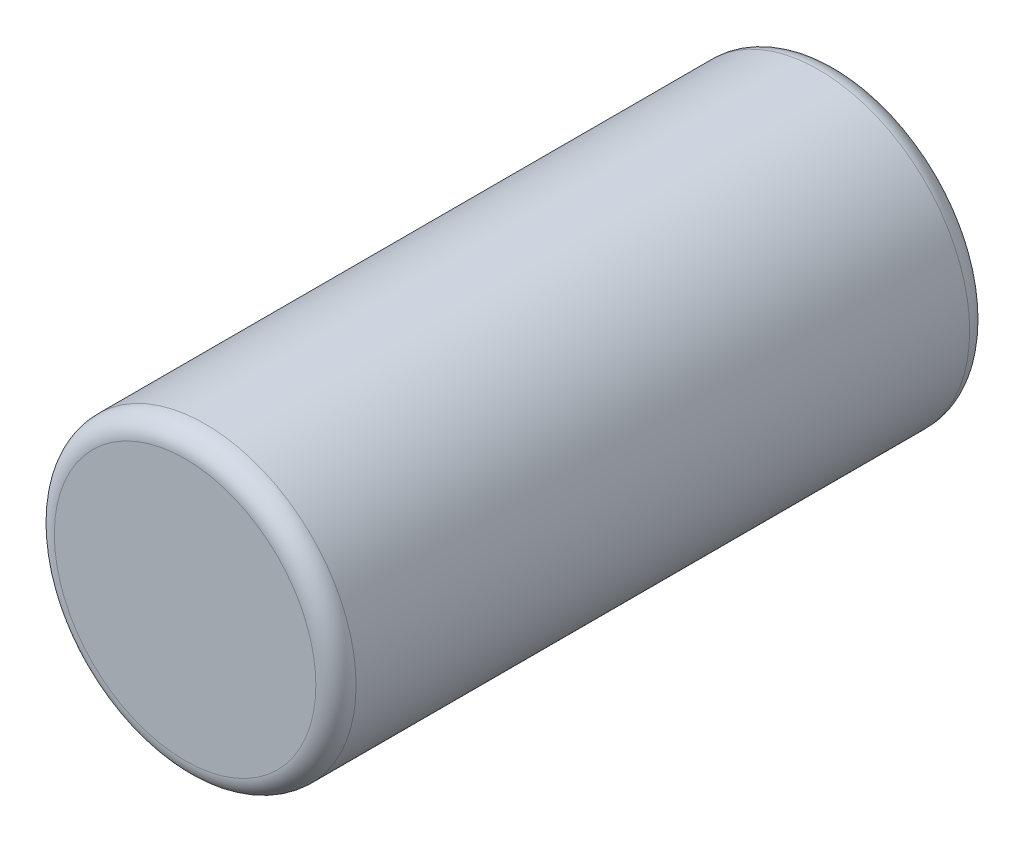
SolidWorks part; units mm, degrees
ref_plane "Спереди" through (0, 0, 0) normal (0, 0, 1) x (1, 0, 0)
ref_plane "Сверху" through (0, 0, 0) normal (0, 1, 0) x (1, 0, 0)
ref_plane "Справа" through (0, 0, 0) normal (1, 0, 0) x (0, 0, -1)
sketch "Эскиз1" plane through (0, 0, 0) normal (0, 0, 1) x (1, 0, 0)
  circle A0 centre (0, 0) radius 1.5
extrude "Бобышка-Вытянуть2" add sketch "Эскиз1" along normal blind 6.5
fillet "Скругление2" radius 0.2 2 edges at (1.5, 0, 0) (1.5, 0, 6.5)
